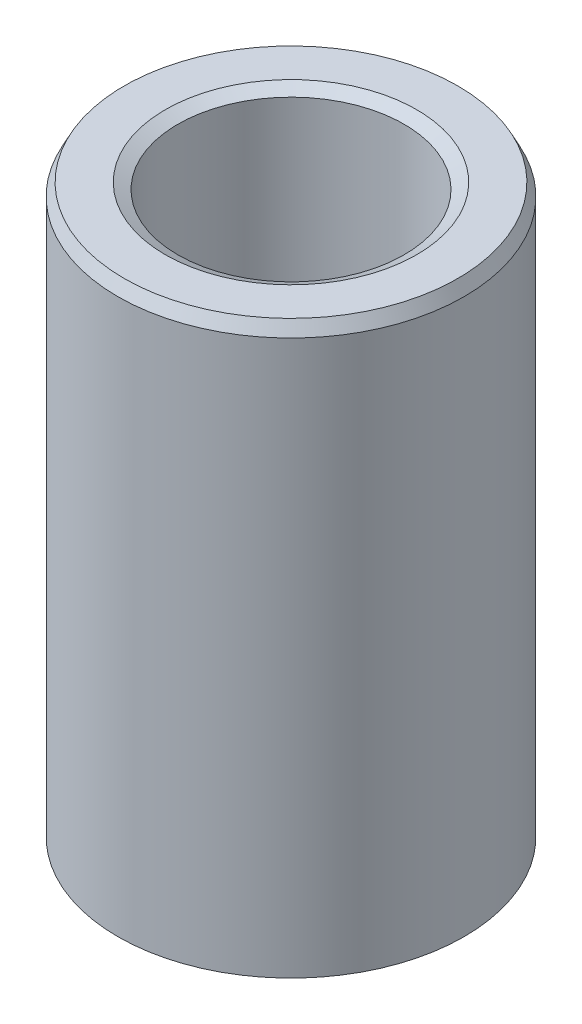
SolidWorks part; units mm, degrees
ref_plane "Front Plane" through (0, 0, 0) normal (0, 0, 1) x (1, 0, 0)
ref_plane "Top Plane" through (0, 0, 0) normal (0, 1, 0) x (1, 0, 0)
ref_plane "Right Plane" through (0, 0, 0) normal (1, 0, 0) x (0, 0, -1)
sketch "Sketch1" plane through (0, 0, 0) normal (0, 1, 0) x (1, 0, 0)
  circle A0 centre (0, 0) radius 35
  dimension "SLEEVE_OD" = 70
extrude "Boss-Extrude1" add sketch "Sketch1" along normal blind 115.8419
sketch "Sketch2" plane through (0, 0, 0) normal (0, 1, 0) x (1, 0, 0)
  circle A0 centre (0, 0) radius 22.8686
  dimension "BORE_D" = 45.7371
extrude "Cut-Extrude1" cut sketch "Sketch2" along normal through all
chamfer "Chamfer1" distance 2.5335 angle 26.873 4 edges at (0, 115.8419, 22.8686) (0, 0, 22.8686) (0, 0, 35) (0, 115.8419, 35) first distance on face at (0, 115.8419, 22.8686) first distance on face at (0, 0, 22.8686) first distance on face at (0, 115.8419, 35)
